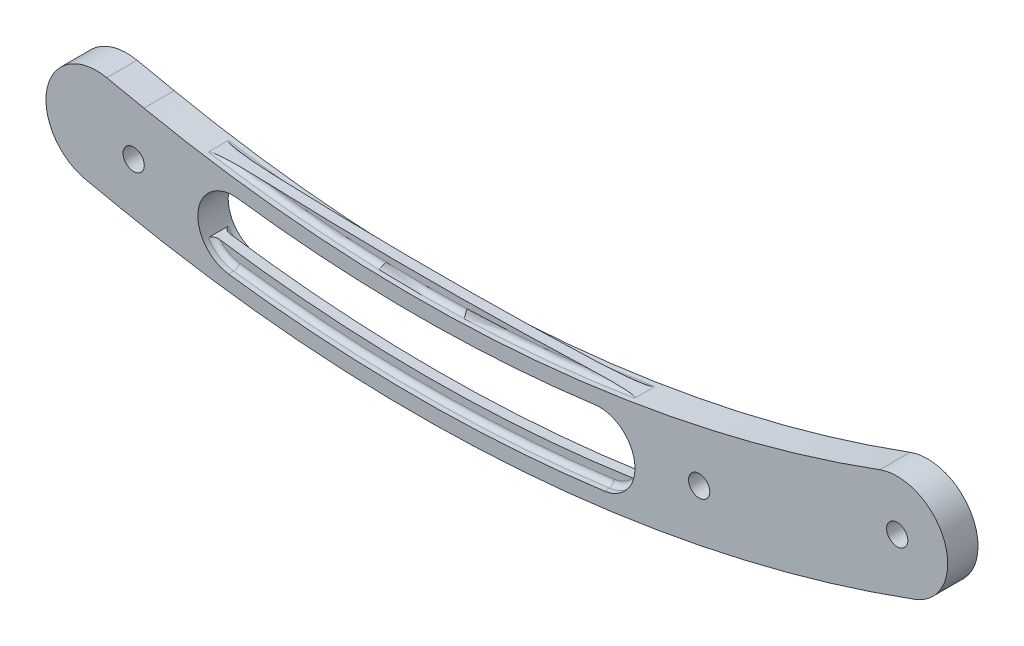
SolidWorks part; units mm, degrees
material "PLA"
ref_plane "Alzado" through (0, 0, 0) normal (0, 0, 1) x (1, 0, 0)
ref_plane "Planta" through (0, 0, 0) normal (0, 1, 0) x (1, 0, 0)
ref_plane "Vista lateral" through (0, 0, 0) normal (1, 0, 0) x (0, 0, -1)
sketch "Croquis1" plane through (0, 0, 0) normal (0, 0, 1) x (1, 0, 0)
  line L0 (-112, 0) -> (0, 0) construction
  line L1 (0, 0) -> (39.2195, 11.246) construction
  line L2 (-121.4057, -8.2581) -> (-114.0359, -9.7906)
  line L4 (-112, 0) -> (-147.4499, 7.3715) construction
  line L5 (-109.9641, 9.7906) -> (-117.3339, 11.3231)
  arc A0 (-112, 0) -> (39.2195, 11.246) centre (-56, 269.3055) ccw construction
  arc A1 (-114.0359, -9.7906) -> (42.6812, 1.8643) centre (-56, 269.3055) ccw
  arc A2 (-109.9641, 9.7906) -> (35.7578, 20.6277) centre (-56, 269.3055) ccw
  arc A3 (-109.9641, 9.7906) -> (-114.0359, -9.7906) centre (-112, 0) ccw
  arc A4 (42.6812, 1.8643) -> (35.7578, 20.6277) centre (39.2195, 11.246) ccw
  circle A5 centre (0, 0) radius 2.1
  circle A6 centre (39.2195, 11.246) radius 2.1
  circle A7 centre (-112, 0) radius 2.1
  arc A8 (-92.2838, -3.3572) -> (-19.7162, -3.3572) centre (-56, 269.3055) ccw construction
  arc A9 (-93.2071, -10.296) -> (-18.7929, -10.296) centre (-56, 269.3055) ccw
  arc A10 (-91.3604, 3.5816) -> (-20.6396, 3.5816) centre (-56, 269.3055) ccw
  arc A11 (-91.3604, 3.5816) -> (-93.2071, -10.296) centre (-92.2838, -3.3572) ccw
  arc A12 (-18.7929, -10.296) -> (-20.6396, 3.5816) centre (-19.7162, -3.3572) ccw
  arc A13 (-121.4057, -8.2581) -> (-117.3339, 11.3231) centre (-119.3698, 1.5325) cw
  point P4 (-35.6, -5.0033)
  point P18 (-56, -5.7608)
  dimension "D4" = 20
  dimension "D5" = 4.2
  dimension "D6" = 4.2
  dimension "D7" = 4.2
  dimension "D9" = 20
  dimension "D10" = 3
  dimension "D1" = 16
  dimension "D2" = 40.8
  dimension "D3" = 112
  dimension "D8" = 20
extrude "Saliente-Extruir1" add sketch "Croquis1" along normal blind 6 contours A1 A4 A2 A3 A12 A9 A11 A10 A7 A6 A5 region at (-120.0755, 1.6792, 0)
ref_plane "Plano6" through (0, 0, 3) normal (0, 0, 1) x (1, 0, 0)
sketch "Croquis3" plane through (0, 0, 3) normal (0, 0, 1) x (1, 0, 0)
  arc A0 (-99.2226, -2.4338) -> (-12.7774, -2.4338) centre (-56, 269.3055) ccw construction
  arc A3 (-98.2286, -7.053) -> (-93.2071, -10.296) centre (-92.2838, -3.3572) ccw
  arc A4 (-93.2071, -10.296) -> (-18.7929, -10.296) centre (-56, 269.3055) ccw
  arc A6 (-98.2286, -7.053) -> (-13.7714, -7.053) centre (-56, 269.3055) ccw
  arc A7 (-13.7714, -7.053) -> (-18.7929, -10.296) centre (-19.7162, -3.3572) cw
  arc A8 (-98.2286, 7.6246) -> (-13.7714, 7.6246) centre (-56, 842.3166) ccw
  arc A9 (-98.2286, 7.6246) -> (-13.7714, 7.6246) centre (-56, 269.3055) ccw
  arc A46 (-109.9641, 9.7906) -> (35.7578, 20.6277) centre (-56, 269.3055) ccw construction
  arc A65 (-18.7929, -10.296) -> (-20.6396, 3.5816) centre (-19.7162, -3.3572) ccw construction
  point P1 (-112, 0)
  point P3 (-56, -10.2608)
  point P4 (-109.9641, 9.7906)
  point P5 (-114.0359, -9.7906)
  point P6 (-56, 269.3055)
  point P7 (-56, -12.7608)
  point P22 (-116.5501, 0.9462)
  point P28 (-114.5142, 10.7367)
  point P29 (-118.586, -8.8444)
  point P30 (-56, 269.3055)
  point P31 (-109.9641, 9.7906)
  point P32 (35.7578, 20.6277)
  point P33 (39.2195, 11.246)
  point P34 (42.6812, 1.8643)
  point P35 (35.7578, 20.6277)
  point P36 (-56, 269.3055)
  point P37 (-114.0359, -9.7906)
  point P38 (42.6812, 1.8643)
  point P39 (0, 0)
  point P40 (2.0082, 0.614)
  point P41 (39.2195, 11.246)
  point P42 (41.2277, 11.86)
  point P43 (-112, 0)
  point P44 (-109.9918, 0.614)
  point P45 (-56, 269.3055)
  point P46 (-91.3604, 3.5816)
  point P47 (-20.6396, 3.5816)
  point P48 (-92.2838, -3.3572)
  point P49 (-91.3604, 3.5816)
  point P50 (-93.2071, -10.296)
  point P51 (-56, 269.3055)
  point P52 (-93.2071, -10.296)
  point P53 (-18.7929, -10.296)
  point P54 (-112, 0)
  point P55 (-109.9641, 9.7906)
  point P56 (-114.0359, -9.7906)
  point P57 (-56, 269.3055)
  point P58 (-109.9641, 9.7906)
  point P59 (35.7578, 20.6277)
  point P60 (39.2195, 11.246)
  point P61 (42.6812, 1.8643)
  point P62 (35.7578, 20.6277)
  point P63 (-56, 269.3055)
  point P64 (-114.0359, -9.7906)
  point P65 (42.6812, 1.8643)
  point P66 (0, 0)
  point P67 (2.0082, 0.614)
  point P68 (39.2195, 11.246)
  point P69 (41.2277, 11.86)
  point P70 (-112, 0)
  point P71 (-109.9918, 0.614)
  point P72 (-56, 269.3055)
  point P73 (-91.3604, 3.5816)
  point P74 (-20.6396, 3.5816)
  point P75 (-92.2838, -3.3572)
  point P76 (-91.3604, 3.5816)
  point P77 (-93.2071, -10.296)
  point P78 (-56, 269.3055)
  point P79 (-93.2071, -10.296)
  point P80 (-18.7929, -10.296)
  point P81 (-19.7162, -3.3572)
  point P82 (-18.7929, -10.296)
  point P83 (-20.6396, 3.5816)
  point P84 (-112, 0)
  point P85 (-109.9641, 9.7906)
  point P86 (-114.0359, -9.7906)
  point P87 (-56, 269.3055)
  point P88 (-109.9641, 9.7906)
  point P89 (35.7578, 20.6277)
  point P90 (39.2195, 11.246)
  point P91 (42.6812, 1.8643)
  point P92 (35.7578, 20.6277)
  point P93 (-56, 269.3055)
  point P94 (-114.0359, -9.7906)
  point P95 (42.6812, 1.8643)
  point P96 (0, 0)
  point P97 (2.0082, 0.614)
  point P98 (39.2195, 11.246)
  point P99 (41.2277, 11.86)
  point P100 (-112, 0)
  point P101 (-109.9918, 0.614)
  point P102 (-56, 269.3055)
  point P103 (-91.3604, 3.5816)
  point P104 (-20.6396, 3.5816)
  point P105 (-92.2838, -3.3572)
  point P106 (-91.3604, 3.5816)
  point P107 (-93.2071, -10.296)
  point P108 (-56, 269.3055)
  point P109 (-93.2071, -10.296)
  point P110 (-18.7929, -10.296)
  point P111 (-19.7162, -3.3572)
  point P112 (-18.7929, -10.296)
  point P113 (-20.6396, 3.5816)
  point P114 (-56, 269.3055)
  point P115 (-112, 0)
  point P116 (39.2195, 11.246)
  point P117 (-56, 269.3055)
  point P118 (-114.0359, -9.7906)
  point P119 (42.6812, 1.8643)
  point P123 (-112, 0)
  point P124 (-109.9641, 9.7906)
  point P125 (-114.0359, -9.7906)
  point P126 (-56, 269.3055)
  point P127 (-109.9641, 9.7906)
  point P128 (35.7578, 20.6277)
  point P129 (39.2195, 11.246)
  point P130 (42.6812, 1.8643)
  point P131 (35.7578, 20.6277)
  point P132 (-56, 269.3055)
  point P133 (-114.0359, -9.7906)
  point P134 (42.6812, 1.8643)
  point P135 (0, 0)
  point P136 (2.0082, 0.614)
  point P137 (39.2195, 11.246)
  point P138 (41.2277, 11.86)
  point P139 (-112, 0)
  point P140 (-109.9918, 0.614)
  point P141 (-56, 269.3055)
  point P142 (-91.3604, 3.5816)
  point P143 (-20.6396, 3.5816)
  point P144 (-92.2838, -3.3572)
  point P145 (-91.3604, 3.5816)
  point P146 (-93.2071, -10.296)
  point P147 (-109.9641, 9.7906)
  point P148 (35.7578, 20.6277)
  point P149 (39.2195, 11.246)
  point P150 (42.6812, 1.8643)
  point P151 (35.7578, 20.6277)
  point P152 (-56, 269.3055)
  point P153 (-114.0359, -9.7906)
  point P154 (42.6812, 1.8643)
  point P155 (0, 0)
  point P156 (2.0082, 0.614)
  point P157 (39.2195, 11.246)
  point P158 (41.2277, 11.86)
  point P159 (-112, 0)
  point P160 (-109.9918, 0.614)
  point P161 (-56, 269.3055)
  point P162 (-91.3604, 3.5816)
  point P163 (-20.6396, 3.5816)
  point P164 (-56, 269.3055)
  point P165 (-93.2071, -10.296)
  point P166 (-18.7929, -10.296)
  dimension "D1" = 2.5
extrude "Saliente-Extruir3" add sketch "Croquis3" along normal mid plane 2
fillet "Redondeo2" radius 1 8 edges at (-96.0814, -9.2375, 2) (-15.9186, -9.2375, 2) (-96.0814, -9.2375, 4) (-15.9186, -9.2375, 4) (-56, -12.7608, 2) (-56, -12.7608, 4) (-56, 4.2392, 2) (-56, 4.2392, 4)
ref_plane "Plano7" through (-18.0537, -42.3407, 0) normal (0.3922, 0.9199, 0) x (0.9199, -0.3922, 0)
ref_plane "Plano8" through (0, 0, -17) normal (0, 0, 1) x (1, 0, 0)
extrude "Saliente-Extruir5" add sketch "Croquis1<3>" along normal up to surface (6 mm away) contours A13 L2 A3 L5 region at (-123.3744, 2.3652, 0) up to face at (-56, -4.0973, 6)
sketch "Croquis1<3>" plane through (0, 0, 0) normal (0, 0, 1) x (1, 0, 0) same geometry as "Croquis1"
